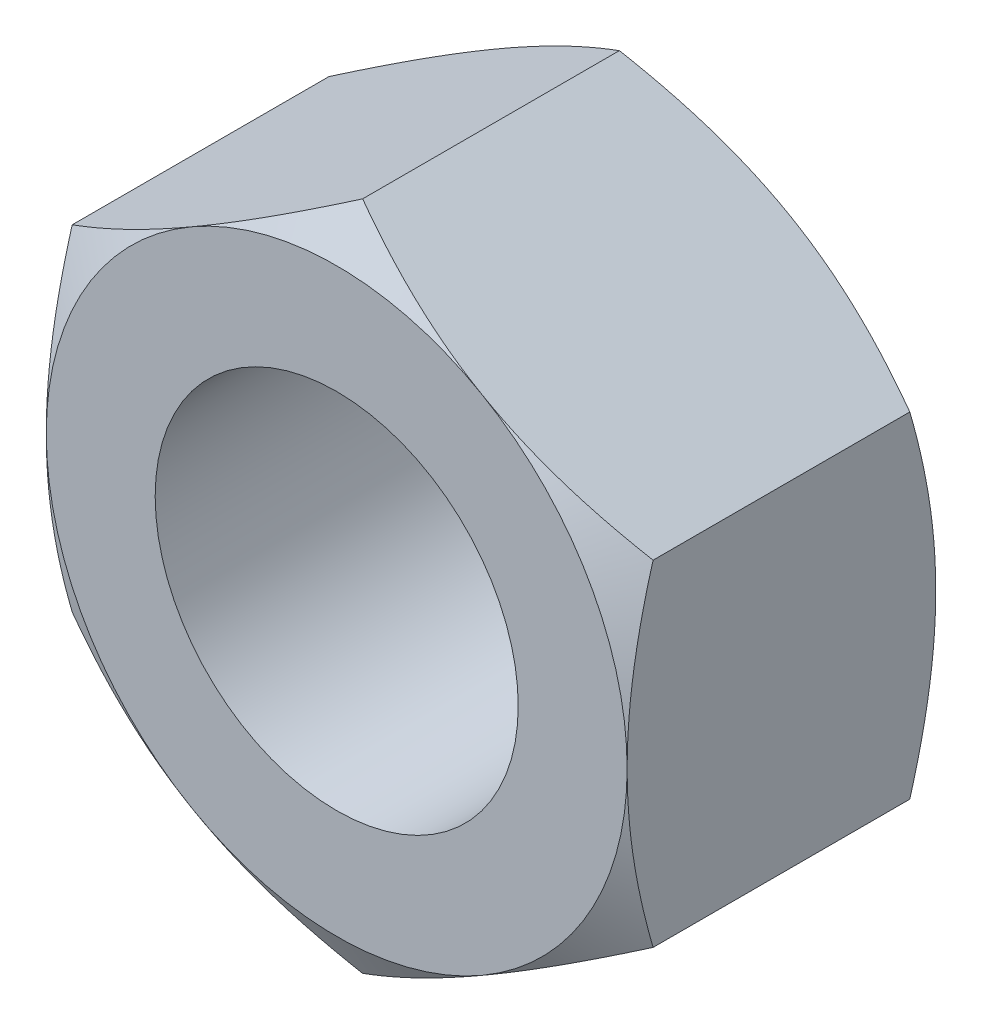
SolidWorks part; units mm, degrees
ref_plane "Front" through (0, 0, 0) normal (0, 0, 1) x (1, 0, 0)
ref_plane "Top" through (0, 0, 0) normal (0, 1, 0) x (1, 0, 0)
ref_plane "Right" through (0, 0, 0) normal (1, 0, 0) x (0, 0, -1)
sketch "Sketch1" plane through (0, 0, 0) normal (0, 0, 1) x (1, 0, 0)
  line L1 (-6.35, 3.6662) -> (-6.35, -3.6662)
  line L2 (-6.35, -3.6662) -> (0, -7.3323)
  line L3 (0, -7.3323) -> (6.35, -3.6662)
  line L4 (6.35, -3.6662) -> (6.35, 3.6662)
  line L5 (6.35, 3.6662) -> (0, 7.3323)
  line L6 (0, 7.3323) -> (-6.35, 3.6662)
  circle A0 centre (0, 0) radius 6.35 construction
  circle A1 centre (0, 0) radius 3.9688
  point P10 (0, 3.9688)
  dimension "hex" = 12.7
  dimension "dia" = 7.9375
extrude "Extrude1" add sketch "Sketch1" along normal mid plane 6.7469
sketch "Sketch4" plane through (0, 0, -3.3734) normal (0, 0, -1) x (-1, 0, 0)
  circle A0 centre (0, 0) radius 3.9688 construction
  circle A1 centre (0, 0) radius 3.9688
curve "Helix/Spiral3" [suppressed] pitch 1.0583 height 8.0962 turns 7.65
sketch "Sketch3" plane through (0, 0, 0) normal (1, 0, 0) x (0, 0, -1)
  line L0 (3.3734, 3.9688) -> (4.2995, 3.9688)
  line L1 (4.2995, 3.9688) -> (3.9026, 3.2813)
  line L2 (3.9026, 3.2813) -> (3.7703, 3.2813)
  line L3 (3.7703, 3.2813) -> (3.3734, 3.9688)
  line L4 (3.5719, 3.625) -> (4.101, 3.625) construction
  dimension "D1" = 60
  dimension "D2" = 0.5292
  dimension "D3" = 0.1323
sweep "Sweep1" [suppressed] add profiles "Sketch3" path "Helix/Spiral3"
sketch "Sketch6" [suppressed] plane through (0, 0, 0) normal (1, 0, 0) x (0, 0, -1)
  line L0 (-3.638, 4.2333) -> (-3.1089, 3.7042)
  line L1 (-3.1089, 3.7042) -> (-3.1089, 0) construction
  line L2 (4.7445, 0) -> (-4.7445, 0) construction
  line L3 (-3.1089, 0) -> (-4.7222, 0)
  line L4 (-4.7222, 0) -> (-4.7222, 4.2333)
  line L5 (-4.7222, 4.2333) -> (-3.638, 4.2333)
  line L6 (-3.1089, 3.7042) -> (0.5953, 0)
  line L7 (0.5953, 0) -> (-3.1089, 0)
  line L8 (-3.3734, -3.6662) -> (-3.3734, 3.6662) construction
  point P2 (-3.3734, 3.9688)
  dimension "D2" = 0.5292
  dimension "D1" = 45
revolve "Cut-Revolve1" [suppressed] cut sketch "Sketch6" angle 360 about L3
sketch "Sketch7" plane through (0, 0, 3.3734) normal (0, 0, 1) x (1, 0, 0)
  circle A0 centre (0, 0) radius 6.35 construction
  circle A1 centre (0, 0) radius 6.35
extrude "Extrude2" cut sketch "Sketch7" against normal blind 25.4 draft 60 flip side to cut
mirror "Mirror1" about plane through (0, 0, 0) normal (0, 0, 1) of "Extrude2", "Cut-Revolve1"
sketch "Sketch8" [suppressed] plane through (0, 0, 3.3734) normal (0, 0, 1) x (1, 0, 0)
  line L0 (-2.8063, 2.8063) -> (0, 0) construction
  line L1 (0, -4.7445) -> (0, 4.7445) construction
  circle A0 centre (0, 0) radius 3.9688 construction
  point P0 (-2.8063, 2.8063)
  dimension "D1" = 45
ref_axis "Axis1" through (0, 0, -3.7108) along (0, 0, 1)
equation "\"D3@Helix/Spiral3\" = \"length@Extrude1\" * 1.2"
equation "\"D2@Sketch3\" = \"D4@Helix/Spiral3\" * .5"
equation "\"D3@Sketch3\" = \"D4@Helix/Spiral3\" * .125"
equation "\"D2@Sketch6\" = \"D4@Helix/Spiral3\" * .5"
